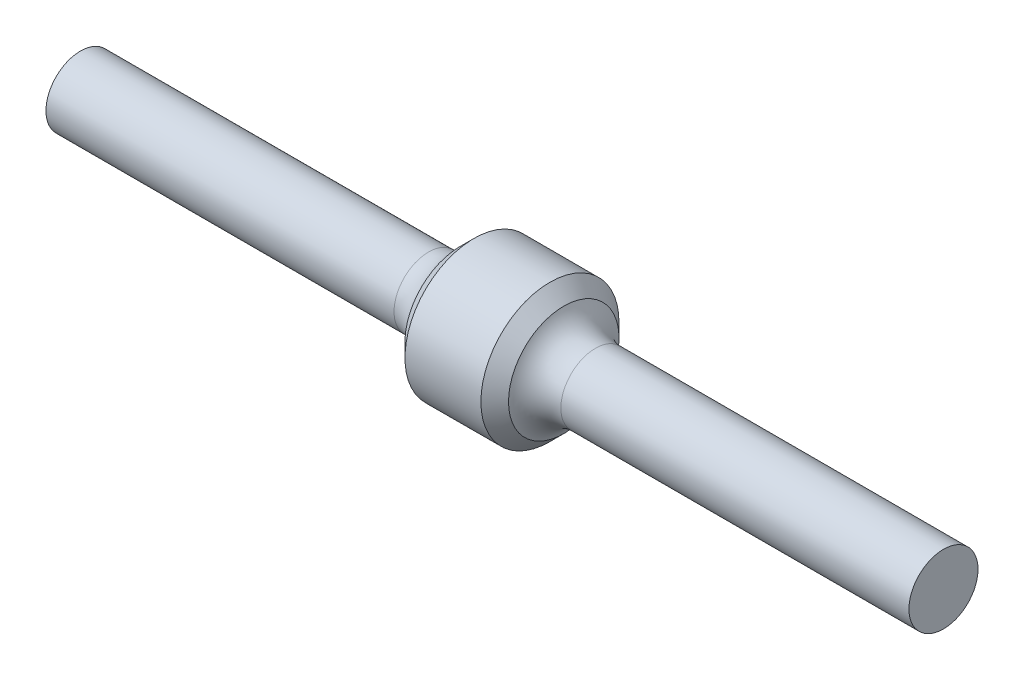
SolidWorks part; units mm, degrees
ref_plane "Front Plane" through (0, 0, 0) normal (0, 0, 1) x (1, 0, 0)
ref_plane "Top Plane" through (0, 0, 0) normal (0, 1, 0) x (1, 0, 0)
ref_plane "Right Plane" through (0, 0, 0) normal (1, 0, 0) x (0, 0, -1)
sketch "Sketch2" plane through (0, 0, 0) normal (1, 0, 0) x (0, 0, -1)
  circle A0 centre (0, 0) radius 5
extrude "Boss-Extrude1" add sketch "Sketch2" along normal mid plane 125
sketch "Sketch3" plane through (0, 0, 0) normal (1, 0, 0) x (0, 0, -1)
  circle A0 centre (0, 0) radius 8
extrude "Boss-Extrude2" add sketch "Sketch3" along normal mid plane 15
fillet "Fillet1" radius 5 2 edges at (-7.5, 0, -5) (7.5, 0, -5)
sketch "Sketch4" plane through (0, 0, 0) normal (1, 0, 0) x (0, 0, -1)
  circle A0 centre (0, 0) radius 10
extrude "Boss-Extrude3" add sketch "Sketch4" along normal mid plane 15
chamfer "Chamfer1" distance 2 angle 45 2 edges at (-7.5, 0, -10) (7.5, 0, -10)
